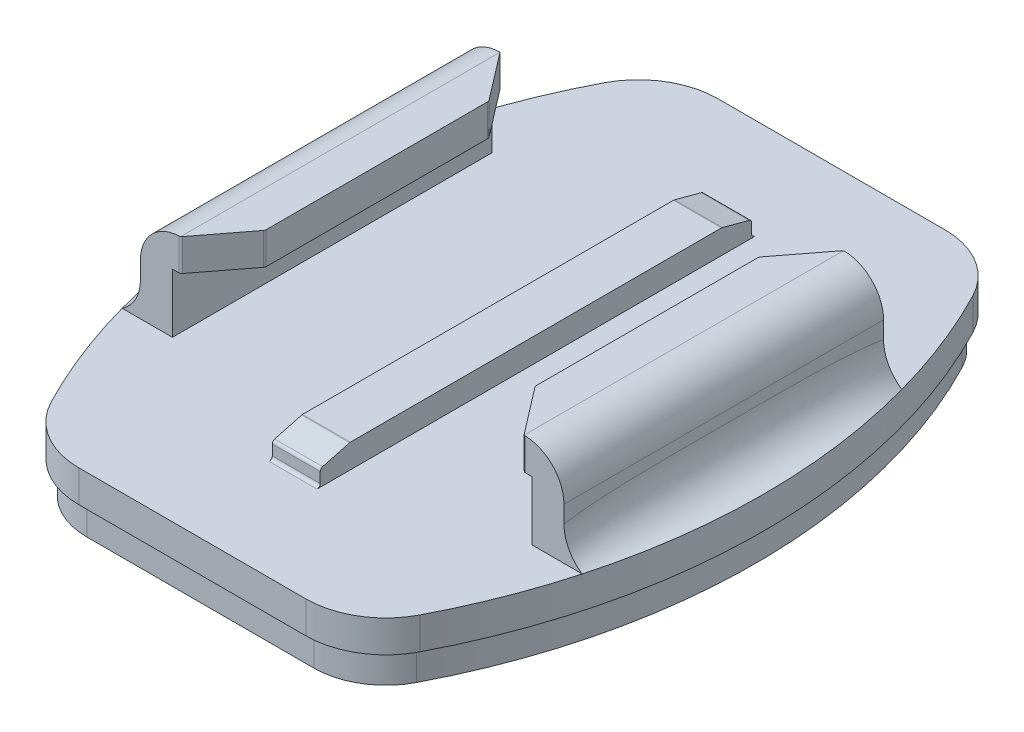
SolidWorks part; units mm, degrees
material "ABS"
ref_plane "Front Plane" through (0, 0, 0) normal (0, 0, 1) x (1, 0, 0)
ref_plane "Top Plane" through (0, 0, 0) normal (0, 1, 0) x (1, 0, 0)
ref_plane "Right Plane" through (0, 0, 0) normal (1, 0, 0) x (0, 0, -1)
sketch "Sketch1" plane through (0, 0, 0) normal (0, 1, 0) x (1, 0, 0)
  line L0 (0, 25.4) -> (0, -25.4) construction
  line L1 (-20.0025, 0) -> (20.0025, 0) construction
  line L2 (-9.0187, 25.4) -> (9.0187, 25.4)
  line L3 (-9.0187, -25.4) -> (9.0187, -25.4)
  arc A0 (-14.6593, 21.9666) -> (-14.6593, -21.9666) centre (27.8227, 0) ccw
  arc A1 (14.6593, 21.9666) -> (14.6593, -21.9666) centre (-27.8227, 0) cw
  arc A2 (-14.6593, -21.9666) -> (-9.0187, -25.4) centre (-9.0187, -19.05) ccw
  arc A3 (14.6593, -21.9666) -> (9.0187, -25.4) centre (9.0187, -19.05) cw
  arc A4 (14.6593, 21.9666) -> (9.0187, 25.4) centre (9.0187, 19.05) ccw
  arc A5 (-9.0187, 25.4) -> (-14.6593, 21.9666) centre (-9.0187, 19.05) ccw
  point P3 (0, 0)
  point P6 (0, 0)
  point P15 (-12.7, -25.4)
  point P18 (12.7, -25.4)
  dimension "D4" = 6.35
  dimension "D1" = 50.8
  dimension "D2" = 40.005
  dimension "D3" = 25.4
extrude "Boss-Extrude1" add sketch "Sketch1" along normal blind 2.54
sketch "Sketch2" plane through (0, 0, 0) normal (0, -1, 0) x (1, 0, 0)
  line L10 (-9.0187, -24.765) -> (9.0187, -24.765)
  line L11 (9.0187, 24.765) -> (-9.0187, 24.765)
  line L12 (-9.0187, -24.765) -> (9.0187, -24.765)
  line L13 (9.0187, 24.765) -> (-9.0187, 24.765)
  arc A36 (-14.0952, -21.675) -> (-9.0187, -24.765) centre (-9.0187, -19.05) ccw
  arc A37 (9.0187, -24.765) -> (14.0952, -21.675) centre (9.0187, -19.05) ccw
  arc A38 (14.0952, -21.675) -> (14.0952, 21.675) centre (-27.8227, 0) ccw
  arc A39 (14.0952, 21.675) -> (9.0187, 24.765) centre (9.0187, 19.05) ccw
  arc A40 (-9.0187, 24.765) -> (-14.0952, 21.675) centre (-9.0187, 19.05) ccw
  arc A41 (-14.0952, 21.675) -> (-14.0952, -21.675) centre (27.8227, 0) ccw
  arc A42 (-14.0952, -21.675) -> (-9.0187, -24.765) centre (-9.0187, -19.05) ccw
  arc A43 (9.0187, -24.765) -> (14.0952, -21.675) centre (9.0187, -19.05) ccw
  arc A44 (14.0952, -21.675) -> (14.0952, 21.675) centre (-27.8227, 0) ccw
  arc A45 (14.0952, 21.675) -> (9.0187, 24.765) centre (9.0187, 19.05) ccw
  arc A46 (-9.0187, 24.765) -> (-14.0952, 21.675) centre (-9.0187, 19.05) ccw
  arc A47 (-14.0952, 21.675) -> (-14.0952, -21.675) centre (27.8227, 0) ccw
  dimension "D1" = 0.635
extrude "Boss-Extrude2" add sketch "Sketch2" along normal blind 2.54 separate body
sketch "Sketch3" plane through (0, 2.54, 0) normal (0, 1, 0) x (1, 0, 0)
  line L0 (0, 17.145) -> (0, -17.145) construction
  line L1 (-1.905, 17.145) -> (-1.905, -17.145)
  line L2 (1.905, 17.145) -> (1.905, -17.145)
  line L3 (-1.905, 17.145) -> (1.905, 17.145)
  line L4 (1.905, -17.145) -> (-1.905, -17.145)
  dimension "D1" = 34.29
  dimension "D2" = 1.905
  dimension "D3" = 1.905
extrude "Boss-Extrude3" add sketch "Sketch3" along normal blind 1.905
sketch "Sketch4" plane through (0, 0, 0) normal (0, 0, 1) x (1, 0, 0)
  line L0 (-14.6593, 2.54) -> (-20.0025, 2.54) construction
  line L1 (-1.905, 4.445) -> (-1.905, 2.54) construction
  line L2 (-14.2875, 2.54) -> (-14.2875, 7.239)
  line L3 (-14.2875, 7.239) -> (-10.7315, 7.239)
  line L4 (-10.7315, 7.239) -> (-10.7315, 9.779)
  line L5 (-10.7315, 9.779) -> (-16.8275, 9.779)
  line L6 (-16.8275, 9.779) -> (-16.8275, 2.54)
  line L7 (-16.8275, 2.54) -> (-14.2875, 2.54)
  line L8 (0, 0) -> (0, 50000) construction
  line L9 (16.8275, 2.54) -> (14.2875, 2.54)
  line L10 (16.8275, 9.779) -> (16.8275, 2.54)
  line L11 (10.7315, 9.779) -> (16.8275, 9.779)
  line L12 (10.7315, 7.239) -> (10.7315, 9.779)
  line L13 (14.2875, 7.239) -> (10.7315, 7.239)
  line L14 (14.2875, 2.54) -> (14.2875, 7.239)
  point P0 (-14.2875, 2.54)
  dimension "D1" = 12.3825
  dimension "D2" = 7.239
  dimension "D3" = 2.54
  dimension "D4" = 2.54
  dimension "D5" = 6.096
extrude "Boss-Extrude4" add sketch "Sketch4" along normal blind 12.7 and the other way blind 12.7
fillet "Fillet1" radius 3.175 4 edges at (16.8275, 2.54, 0) (-16.8275, 2.54, 0) (16.8275, 9.779, 0) (-16.8275, 9.779, 0)
sketch "Sketch5" plane through (0, 9.779, 0) normal (0, 1, 0) x (1, 0, 0)
  line L0 (-13.6525, 12.7) -> (-10.7315, 8.89)
  line L1 (-10.7315, 12.7) -> (-10.7315, -12.7) construction
  line L2 (-10.7315, 12.7) -> (-13.6525, 12.7) construction
  line L3 (-13.6525, 12.7) -> (-10.7315, 12.7)
  line L4 (-10.7315, 12.7) -> (-10.7315, 8.89)
  line L5 (-13.6525, -12.7) -> (-10.7315, -8.89)
  line L6 (-10.7315, -8.89) -> (-10.7315, -12.7)
  line L7 (-10.7315, -12.7) -> (-13.6525, -12.7) construction
  line L8 (-10.7315, -12.7) -> (-13.6525, -12.7)
  line L9 (0, -17.145) -> (0, 17.145) construction
  line L10 (-1.905, -17.145) -> (1.905, -17.145) construction
  line L11 (1.905, 17.145) -> (-1.905, 17.145) construction
  line L12 (10.7315, -12.7) -> (13.6525, -12.7)
  line L13 (10.7315, -8.89) -> (10.7315, -12.7)
  line L14 (13.6525, -12.7) -> (10.7315, -8.89)
  line L15 (10.7315, 12.7) -> (10.7315, 8.89)
  line L16 (13.6525, 12.7) -> (10.7315, 12.7)
  line L17 (13.6525, 12.7) -> (10.7315, 8.89)
  dimension "D1" = 3.81
  dimension "D2" = 3.81
extrude "Cut-Extrude1" cut sketch "Sketch5" against normal up to surface (7.239 mm away) up to face at (0, 2.54, 0)
chamfer "Chamfer1" distance 0.635 angle 75 2 edges at (0, 4.445, -17.145) (0, 4.445, 17.145) first distance on face at (0, 3.4925, -17.145) first distance on face at (0, 3.4925, 17.145)
fillet "Fillet2" radius 0.254 13 edges at (10.7315, 8.509, -8.89) (13.6525, 8.509, -12.7) (10.7315, 8.509, 8.89) (13.6525, 8.509, 12.7) (-10.7315, 8.509, -8.89) (-13.6525, 8.509, 12.7) (-10.7315, 8.509, 8.89) (0, 2.54, -17.145) (0, 2.54, 17.145) (0, 3.81, -17.145) (0, 3.81, 17.145) (0, 4.445, -14.7751) (0, 4.445, 14.7751)
